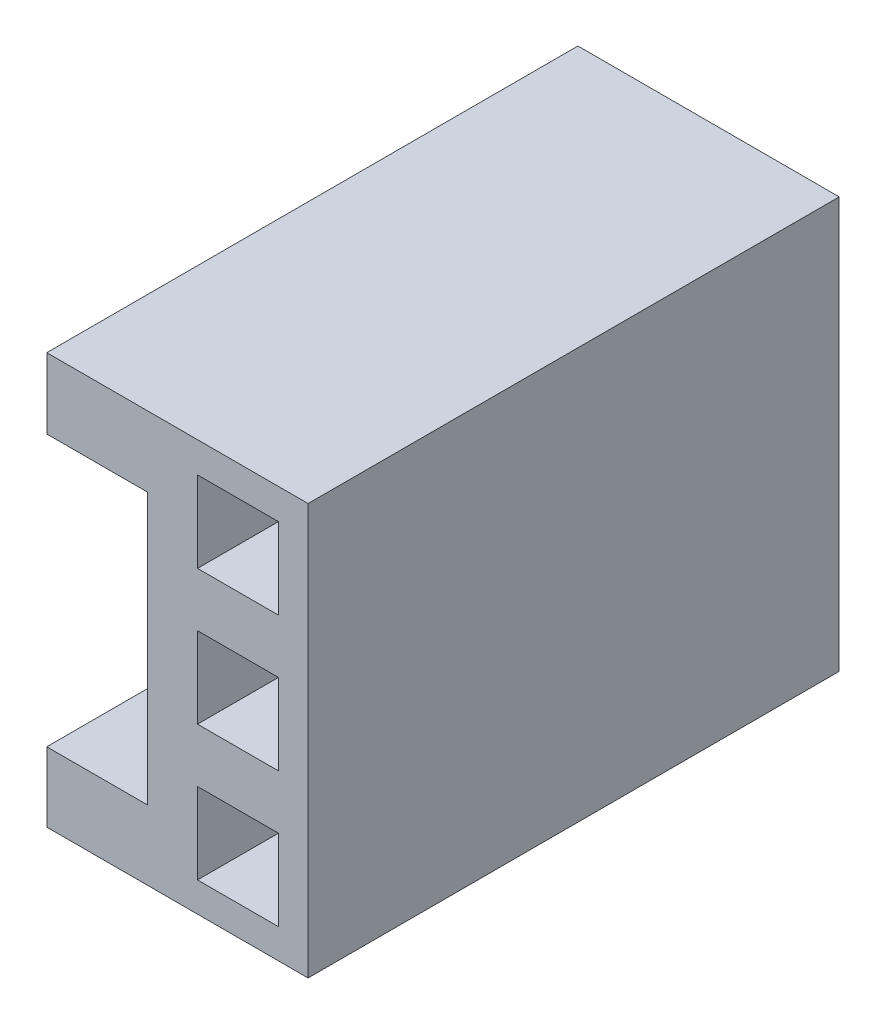
SolidWorks part; units mm, degrees
ref_plane "Front Plane" through (0, 0, 0) normal (0, 0, 1) x (1, 0, 0)
ref_plane "Top Plane" through (0, 0, 0) normal (0, 1, 0) x (1, 0, 0)
ref_plane "Right Plane" through (0, 0, 0) normal (1, 0, 0) x (0, 0, -1)
sketch "Sketch1" plane through (0, 0, 0) normal (0, 0, 1) x (1, 0, 0)
  line L0 (0.32, 0.32) -> (-0.32, -0.32) construction
  line L8 (-3.6, 3.876) -> (-3.6, -3.86)
  line L9 (-3.6, -3.86) -> (1.32, -3.86)
  line L10 (1.32, -3.86) -> (1.32, 3.876)
  line L11 (1.32, 3.876) -> (-3.6, 3.876)
  line L16 (-2.6, 2.55) -> (-2.6, -2.55)
  line L17 (-1.7, 2.55) -> (-2.6, 2.55)
  line L18 (-1.7, -2.55) -> (-1.7, 2.55)
  line L19 (-2.6, -2.55) -> (-1.7, -2.55)
  line L24 (-0.32, 2.86) -> (-0.32, 2.22)
  line L25 (0.32, 2.86) -> (-0.32, 2.86)
  line L26 (0.32, 2.22) -> (0.32, 2.86)
  line L27 (-0.32, 2.22) -> (0.32, 2.22)
  line L32 (-0.32, 0.32) -> (-0.32, -0.32)
  line L33 (-0.32, -0.32) -> (0.32, -0.32)
  line L34 (0.32, -0.32) -> (0.32, 0.32)
  line L35 (0.32, 0.32) -> (-0.32, 0.32)
  line L40 (-0.32, -2.22) -> (-0.32, -2.86)
  line L41 (-0.32, -2.86) -> (0.32, -2.86)
  line L42 (0.32, -2.86) -> (0.32, -2.22)
  line L43 (0.32, -2.22) -> (-0.32, -2.22)
  dimension "D2" = 4.92
  dimension "D3" = 0.64
  dimension "D4" = 1
  dimension "D5" = 2.54
  dimension "D6" = 5.08
  dimension "D7" = 1
  dimension "D8" = 3.02
  dimension "D9" = 0.9
  dimension "D10" = 5.1
  dimension "D11" = 1.31
  dimension "D12" = 1.016
extrude "Extrude1" add sketch "Sketch1" along normal blind 10
sketch "Sketch3" plane through (0, 0, 10) normal (0, 0, 1) x (1, 0, 0)
  line L0 (-0.32, -2.22) -> (0.32, -2.86) construction
  line L1 (-0.762, -3.302) -> (0.762, -3.302)
  line L2 (-0.762, -3.302) -> (-0.762, -1.778)
  line L3 (-0.762, -1.778) -> (0.762, -1.778)
  line L4 (0.762, -3.302) -> (0.762, -1.778)
  line L5 (0.762, -1.778) -> (-0.762, -3.302) construction
  point P6 (0, -2.54)
  dimension "D1" = 1.524
extrude "Cut-Extrude1" cut sketch "Sketch3" against normal blind 2.54
pattern_linear "LPattern1" count 3 spacing 2.54 along (0, 1, 0) of "Cut-Extrude1"
sketch "Sketch4" plane through (-2.6, 0, 0) normal (1, 0, 0) x (0, 0, -1)
  line L4 (0, -2.55) -> (0, 2.55)
  line L5 (0, 2.55) -> (-10, 2.55)
  line L6 (-10, 2.55) -> (-10, -2.55)
  line L7 (-10, -2.55) -> (0, -2.55)
  line L8 (0, -2.55) -> (0, 2.55)
  line L9 (0, 2.55) -> (-10, 2.55)
  line L10 (-10, 2.55) -> (-10, -2.55)
  line L11 (-10, -2.55) -> (0, -2.55)
  dimension "D1" = 0
extrude "Cut-Extrude2" cut sketch "Sketch4" against normal through all
sketch "Sketch5" plane through (0, 2.55, 0) normal (0, -1, 0) x (1, 0, 0)
  line L3 (-1.45, 2.5) -> (-1.7, 2)
  line L4 (-1.45, 3.5) -> (-1.45, 2.5)
  line L5 (-1.7, 4) -> (-1.45, 3.5)
  line L6 (-1.7, 2) -> (-1.7, 4)
  line L8 (-1.7, 10) -> (-1.7, 0) construction
  dimension "D1" = 2
  dimension "D2" = 2
  dimension "D3" = 0.25
  dimension "D4" = 26.565
extrude "Cut-Extrude3" cut sketch "Sketch5" along normal up to surface (5.1 mm away) up to face at (-2.65, -2.55, 5)
sketch "Sketch6" plane through (0, 0, 10) normal (0, 0, 1) x (1, 0, 0)
  point P0 (0, 0)
other "CPoint2" parameters "Diameter"=5, "StubLength"=7
ref_axis "Axis2" through (0, 0, 20) along (0, 0, -1)
